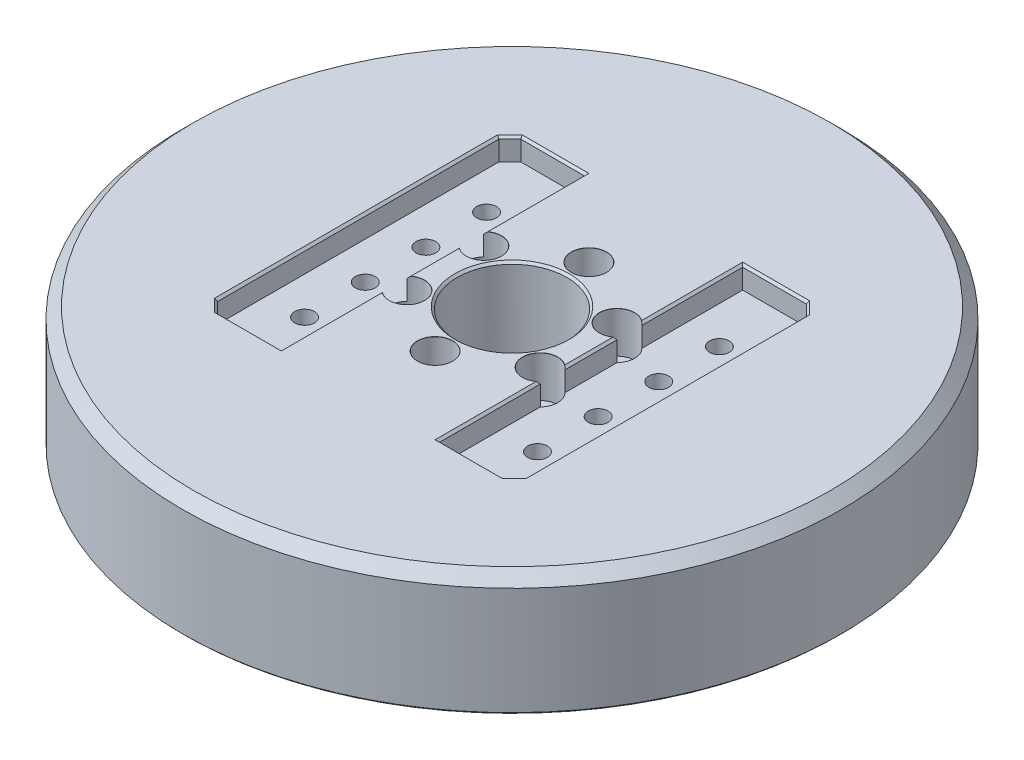
SolidWorks part; units mm, degrees
ref_plane "Ebene vorne" through (0, 0, 0) normal (0, 0, 1) x (1, 0, 0)
ref_plane "Ebene oben" through (0, 0, 0) normal (0, 1, 0) x (1, 0, 0)
ref_plane "Ebene rechts" through (0, 0, 0) normal (1, 0, 0) x (0, 0, -1)
sketch "Sketch1" plane through (0, 0, 0) normal (0, 0, 1) x (1, 0, 0)
  line L0 (0, 0) -> (0, 50) construction
  line L1 (12.5, 0) -> (75, 0)
  line L2 (75, 0) -> (75, -27.5)
  line L3 (75, -27.5) -> (72.5, -27.5)
  line L4 (72.5, -27.5) -> (72.5, -20)
  line L5 (72.5, -20) -> (24, -20)
  line L6 (24, -20) -> (24, -20.5)
  line L7 (24, -20.5) -> (22.5, -20.5)
  line L8 (22.5, -20.5) -> (22.5, -20)
  line L9 (22.5, -20) -> (12.5, -20)
  line L10 (12.5, -20) -> (12.5, 0)
  point P5 (24, -20.25)
  dimension "D1" = 50
  dimension "D2" = 150
  dimension "D3" = 20
  dimension "D4" = 25
  dimension "D5" = 48
  dimension "D6" = 45
  dimension "D7" = 0.5
  dimension "D8" = 145
  dimension "D9" = 7.5
revolve "Revolve1" add sketch "Sketch1" angle 360 about L0
sketch "Sketch2" plane through (0, 0, 0) normal (0, 1, 0) x (1, 0, 0)
  line L1 (-35, -34.5) -> (-18, -34.5)
  line L2 (-35, -34.5) -> (-35, 34.5)
  line L3 (-35, 34.5) -> (-18, 34.5)
  line L4 (-18, -34.5) -> (-18, 34.5)
  line L5 (-35, -34.5) -> (-18, 34.5) construction
  line L6 (-35, 34.5) -> (-18, -34.5) construction
  line L7 (18, -34.5) -> (35, -34.5)
  line L8 (18, -34.5) -> (18, 34.5)
  line L9 (18, 34.5) -> (35, 34.5)
  line L10 (35, -34.5) -> (35, 34.5)
  line L11 (18, -34.5) -> (35, 34.5) construction
  line L12 (18, 34.5) -> (35, -34.5) construction
  point P0 (-26.5, 0)
  point P5 (26.5, 0)
  dimension "D1" = 17
  dimension "D2" = 17
  dimension "D3" = 36
  dimension "D4" = 69
  dimension "D5" = 18
extrude "Cut-Extrude1" cut sketch "Sketch2" against normal blind 5
hole_wizard "CBORE for M4 Hex Socket Head Cap Screw1" positions "Sketch5" profile "Sketch6" counterbore size "M4" standard "DIN"
sketch "Sketch5" plane through (0, -20.5, 0) normal (0, -1, 0) x (-1, 0, 0)
  line L0 (-35, -34.5) -> (-35, 34.5) construction
  line L1 (-35, 34.5) -> (-18, 34.5) construction
  line L2 (-18, 34.5) -> (-18, -34.5) construction
  line L3 (-18, -34.5) -> (-35, -34.5) construction
  line L4 (18, -34.5) -> (18, 34.5) construction
  line L5 (18, 34.5) -> (35, 34.5) construction
  line L6 (35, 34.5) -> (35, -34.5) construction
  line L7 (35, -34.5) -> (18, -34.5) construction
  line L8 (-35, -34.5) -> (-35, 34.5)
  line L9 (-35, 34.5) -> (-18, 34.5)
  line L10 (-18, 34.5) -> (-18, -34.5)
  line L11 (-18, -34.5) -> (-35, -34.5)
  line L12 (18, -34.5) -> (18, 34.5)
  line L13 (18, 34.5) -> (35, 34.5)
  line L14 (35, 34.5) -> (35, -34.5)
  line L15 (35, -34.5) -> (18, -34.5)
  line L16 (26.5, 34.5) -> (26.5, -34.5) construction
  line L18 (-26.5, 34.5) -> (-26.5, -34.5) construction
  point P16 (26.5, -34.5)
  point P31 (26.5, -20.7)
  point P32 (26.5, -6.9)
  point P33 (26.5, 6.9)
  point P34 (26.5, 20.7)
  point P49 (-26.5, -34.5)
  point P50 (-26.5, -20.7)
  point P52 (-26.5, -6.9)
  point P54 (-26.5, 6.9)
  point P58 (-26.5, 20.7)
sketch "Sketch6" plane through (26.5, -20.5, -20.7) normal (1, 0, 0) x (0, 0, -1)
  line L0 (0, 0) -> (0, 20.5)
  line L1 (0, 20.5) -> (2.25, 20.5)
  line L3 (2.25, 20.5) -> (2.25, 4.9)
  line L4 (2.25, 4.9) -> (4, 4.9)
  line L5 (4, 4.9) -> (4, 0)
  line L7 (4, 0) -> (0, 0)
  line L11 (0, -6.35) -> (0, 107.95) construction
  dimension "Thru Hole Dia." = 4.5
  dimension "Thru Hole Depth" = 20.5
  dimension "C'Bore Dia." = 8
  dimension "C'Bore Depth" = 4.9
hole_wizard "CBORE for M4 Hex Socket Head Cap Screw2" positions "Sketch7" profile "Sketch8" counterbore size "M4" standard "DIN" end condition through all
sketch "Sketch7" plane through (0, 0, 0) normal (0, 1, 0) x (1, 0, 0)
  circle A0 centre (0, 0) radius 17.5
  point P5 (0, -17.5)
  point P11 (-15.1554, -8.75)
  point P12 (-15.1554, 8.75)
  point P13 (0, 17.5)
  point P14 (15.1554, 8.75)
  point P15 (15.1554, -8.75)
  dimension "D1" = 35
  dimension "D2" = 6
sketch "Sketch8" plane through (15.1554, 0, 8.75) normal (1, 0, 0) x (0, 0, 1)
  line L0 (0, 0) -> (0, 27.5)
  line L1 (0, 27.5) -> (2.25, 27.5)
  line L3 (2.25, 27.5) -> (2.25, 9.4)
  line L4 (4, 9.4) -> (2.25, 9.4)
  line L5 (4, 9.4) -> (4, 0.025)
  line L6 (4, 0.025) -> (4.025, 0)
  line L7 (4.025, 0) -> (0, 0)
  line L8 (-4, 0.025) -> (-4.025, 0) construction
  line L11 (0, -6.35) -> (0, 107.95) construction
  dimension "Thru Hole Dia." = 4.5
  dimension "Thru Hole Depth" = 27.5
  dimension "C'Bore Dia." = 8
  dimension "C'Bore Depth" = 9.4
  dimension "Near C'Sink Dia." = 8.05
  dimension "Near C'Sink Angle" = 90
chamfer "2,5mm Chamfer1" distance 2.5 angle 45 5 edges at (-35, -2.5, 34.5) (-35, -2.5, -34.5) (35, -2.5, -34.5) (35, -2.5, 34.5) (0, 0, -75)
chamfer "0,5mm Chamfer2" distance 0.5 angle 45 20 edges at (-25.25, 0, -34.5) (-33.75, 0, -33.25) (0, -20, -12.5) (0, 0, -12.5) (0, -27.5, -72.5) (0, -27.5, -75) (18, 0, 0) (18, 0, 23.0488) (25.25, 0, 34.5) (33.75, 0, 33.25) (35, 0, 0) (18, 0, -23.0488) (33.75, 0, -33.25) (25.25, 0, -34.5) (-18, 0, 0) (-18, 0, 23.0488) (-25.25, 0, 34.5) (-33.75, 0, 33.25) (-35, 0, 0) (-18, 0, -23.0488)
